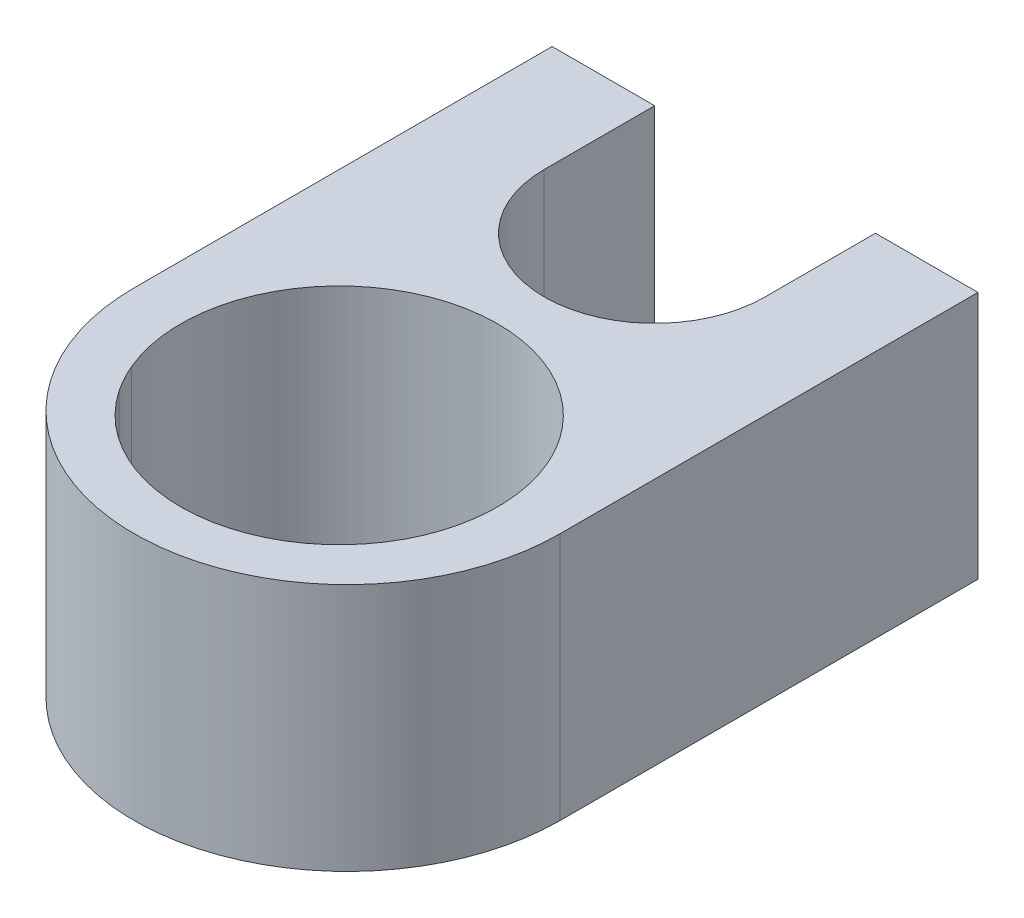
SolidWorks part; units mm, degrees
ref_plane "Płaszczyzna przednia" through (0, 0, 0) normal (0, 0, 1) x (1, 0, 0)
ref_plane "Płaszczyzna górna" through (0, 0, 0) normal (0, 1, 0) x (1, 0, 0)
ref_plane "Płaszczyzna prawa" through (0, 0, 0) normal (1, 0, 0) x (0, 0, -1)
sketch "Szkic1" plane through (0, 0, 0) normal (0, 0, 1) x (1, 0, 0)
  line L1 (-27, -15.75) -> (27, -15.75)
  line L2 (-27, -15.75) -> (-27, 15.75)
  line L3 (-27, 15.75) -> (27, 15.75)
  line L4 (27, -15.75) -> (27, 15.75)
  line L5 (-27, -15.75) -> (27, 15.75) construction
  line L6 (-27, 15.75) -> (27, -15.75) construction
  point P0 (0, 0)
  dimension "D1" = 54
  dimension "D2" = 31.5
extrude "Dodanie-wyciągnięcie1" add sketch "Szkic1" along normal blind 45
sketch "Szkic2" plane through (0, 0, 0) normal (0, 0, -1) x (-1, 0, 0)
  line L16 (-27, 15.75) -> (-27, -15.75)
  line L17 (-27, -15.75) -> (27, -15.75)
  line L18 (27, -15.75) -> (27, 15.75)
  line L19 (27, 15.75) -> (-27, 15.75)
  line L20 (-27, 15.75) -> (-27, -15.75)
  line L21 (-27, -15.75) -> (27, -15.75)
  line L22 (27, -15.75) -> (27, 15.75)
  line L23 (27, 15.75) -> (-27, 15.75)
  dimension "D1" = 0
extrude "Dodanie-wyciągnięcie2" add sketch "Szkic2" along normal blind 35
ref_plane "Płaszczyzna1" through (0, 0, 0) normal (0, 1, 0) x (1, 0, 0)
sketch "Szkic8" plane through (0, 15.75, 0) normal (0, 1, 0) x (1, 0, 0)
  line L0 (14, 35) -> (-14, 35)
  line L2 (14, 35) -> (14, 21)
  line L4 (-14, 35) -> (-14, 21)
  line L5 (-27, 35) -> (27, 35) construction
  arc A0 (14, 21) -> (-14, 21) centre (0, 21) cw
  point P4 (0, 35)
  dimension "D1" = 14
  dimension "D2" = 14
extrude "Wytnij-wyciągnięcie3" cut sketch "Szkic8" against normal up to next contours L4 A0 L2 L0
ref_plane "Płaszczyzna2" through (0, 0, 80) normal (0, 0, 1) x (1, 0, 0)
sketch "Szkic9" plane through (0, -15.75, 0) normal (0, -1, 0) x (-1, 0, 0)
  circle A0 centre (0, -19) radius 20.1
  arc A1 (-14, 21) -> (14, 21) centre (0, 21) ccw construction
  dimension "D1" = 40.2
  dimension "D2" = 40
fillet "Zaokrąglenie1" 2 edges at (-27, 0, 45) (27, 0, 45) type full round first side face at (-27, 0, 5) second side face at (27, 0, 5) middle face at (0, 0, 45)
extrude "Wytnij-wyciągnięcie4" cut sketch "Szkic9" against normal through all contours A0
sketch "Szkic10" plane through (0, 15.75, 0) normal (0, 1, 0) x (1, 0, 0)
  line L0 (0, -19) -> (115, -19)
  line L1 (115, -19) -> (115, -230)
  line L2 (115, -230) -> (0, -19)
ref_plane "Płaszczyzna3" through (115, 15.75, 230) normal (-0.4786, 0, -0.8781) x (-0.8781, 0, 0.4786)
sketch "Szkic11" plane through (115, 15.75, 230) normal (-0.4786, 0, -0.8781) x (-0.8781, 0, 0.4786)
  line L0 (26.5214, 0) -> (-24.186, 0) construction
  line L1 (-20, -31.5) -> (20, -31.5)
  line L2 (-20, -31.5) -> (-20, 0)
  line L3 (-20, 0) -> (20, 0)
  line L4 (20, -31.5) -> (20, 0)
  line L5 (-20, -31.5) -> (20, 0) construction
  line L6 (-20, 0) -> (20, -31.5) construction
  line L7 (-24.186, -31.5) -> (26.5214, -31.5) construction
  point P0 (0, -15.75)
  dimension "D1" = 40
split line "Linia podziałowa1"
